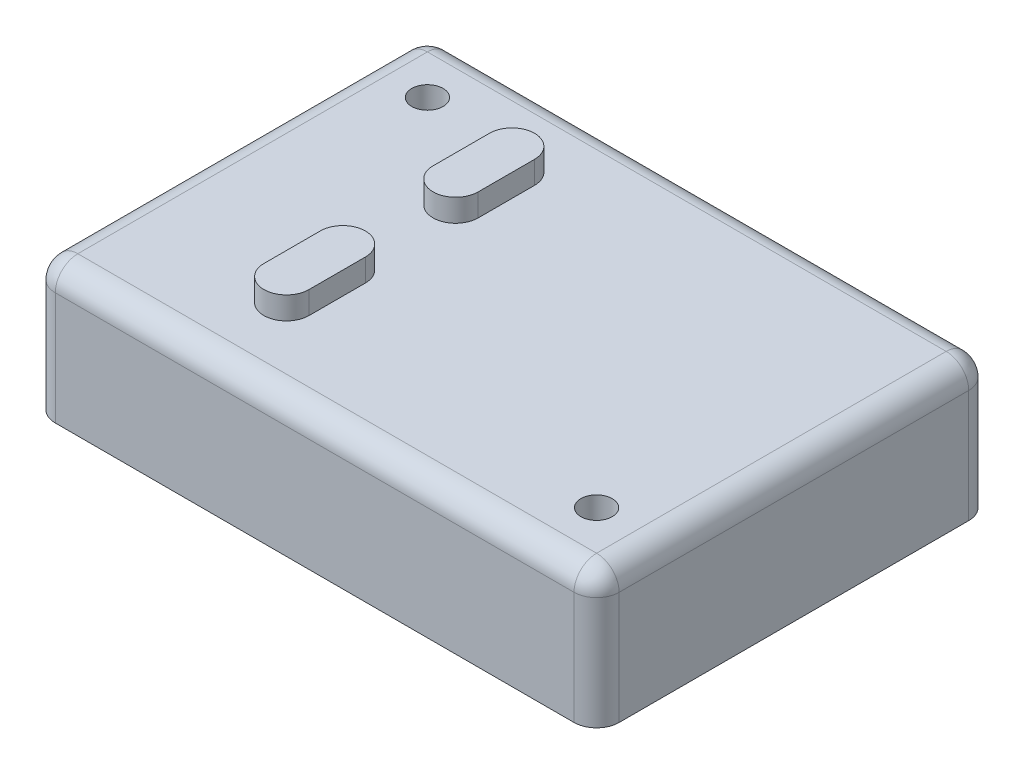
SolidWorks part; units mm, degrees
ref_plane "Front Plane" through (0, 0, 0) normal (0, 0, 1) x (1, 0, 0)
ref_plane "Top Plane" through (0, 0, 0) normal (0, 1, 0) x (1, 0, 0)
ref_plane "Right Plane" through (0, 0, 0) normal (1, 0, 0) x (0, 0, -1)
sketch "Sketch1" plane through (0, 0, 0) normal (0, 1, 0) x (1, 0, 0)
  line L1 (-25, -17.5) -> (25, -17.5)
  line L2 (-25, -17.5) -> (-25, 17.5)
  line L3 (-25, 17.5) -> (25, 17.5)
  line L4 (25, -17.5) -> (25, 17.5)
  line L5 (-25, -17.5) -> (25, 17.5) construction
  line L6 (-25, 17.5) -> (25, -17.5) construction
  point P0 (0, 0)
  dimension "D1" = 50
  dimension "D2" = 35
extrude "Boss-Extrude1" add sketch "Sketch1" along normal blind 12
sketch "Sketch2" plane through (0, 12, 0) normal (0, 1, 0) x (1, 0, 0)
  line L0 (-10, 10) -> (-10, 5) construction
  line L1 (-8, 10) -> (-8, 5)
  line L2 (-12, 10) -> (-12, 5)
  line L3 (-10, -5) -> (-10, -10) construction
  line L4 (-8, -5) -> (-8, -10)
  line L5 (-12, -5) -> (-12, -10)
  arc A0 (-8, 10) -> (-12, 10) centre (-10, 10) ccw
  arc A1 (-12, 5) -> (-8, 5) centre (-10, 5) ccw
  arc A2 (-8, -5) -> (-12, -5) centre (-10, -5) ccw
  arc A3 (-12, -10) -> (-8, -10) centre (-10, -10) ccw
  point P2 (-10, 7.5)
  point P7 (-10, -7.5)
  dimension "D3" = 2
  dimension "D1" = 15
  dimension "D2" = 7.5
  dimension "D4" = 5
  dimension "D5" = 10
extrude "Boss-Extrude2" add sketch "Sketch2" along normal blind 2
fillet "Fillet1" radius 2 8 edges at (-25, 12, 0) (0, 12, -17.5) (-25, 6, -17.5) (25, 12, 0) (25, 6, -17.5) (-25, 6, 17.5) (0, 12, 17.5) (25, 6, 17.5)
sketch "Sketch4" plane through (0, 0, 0) normal (0, -1, 0) x (1, 0, 0)
  line L0 (-23, 17.5) -> (23, 17.5) construction
  line L1 (25, 15.5) -> (25, -15.5) construction
  line L2 (-25, -15.5) -> (-25, 15.5) construction
  line L3 (23, -17.5) -> (-23, -17.5) construction
  circle A0 centre (-19.5, -12) radius 1.39
  circle A1 centre (19.5, 12) radius 1.39
  dimension "D1" = 2.78
  dimension "D2" = 5.5
  dimension "D3" = 5.5
  dimension "D4" = 5.5
  dimension "D5" = 5.5
extrude "Cut-Extrude1" cut sketch "Sketch4" against normal through all
equation "\"D2@Sketch2\"=\"D1@Sketch2\"/2"
